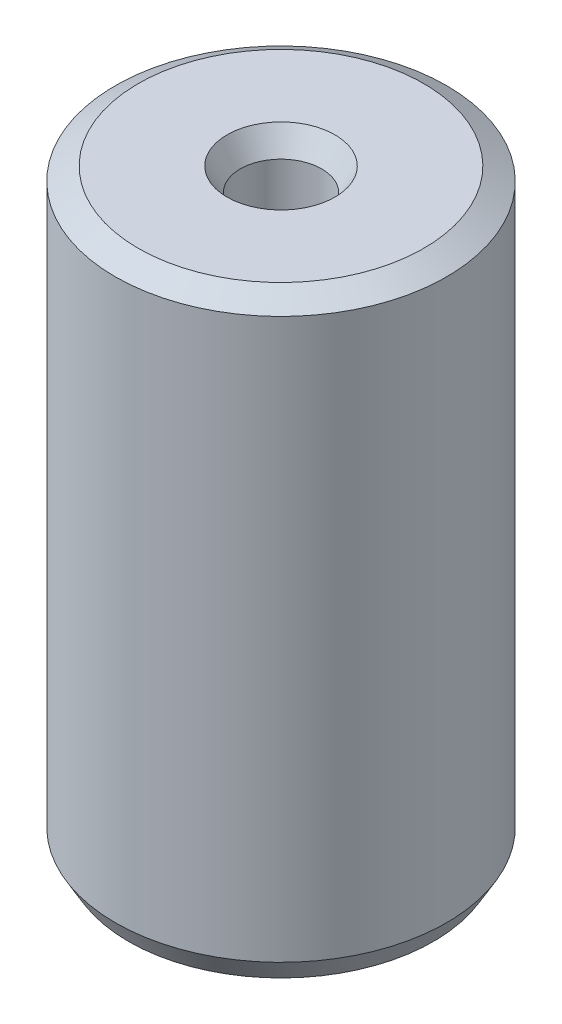
SolidWorks part; units mm, degrees
ref_plane "Front Plane" through (0, 0, 0) normal (0, 0, 1) x (1, 0, 0)
ref_plane "Top Plane" through (0, 0, 0) normal (0, 1, 0) x (1, 0, 0)
ref_plane "Right Plane" through (0, 0, 0) normal (1, 0, 0) x (0, 0, -1)
sketch "Sketch1" plane through (0, 0, 0) normal (0, 1, 0) x (1, 0, 0)
  circle A0 centre (0, 0) radius 5
  dimension "SLEEVE_OD" = 10
extrude "Boss-Extrude1" add sketch "Sketch1" along normal blind 17.9749
sketch "Sketch2" plane through (0, 0, 0) normal (0, 1, 0) x (1, 0, 0)
  circle A0 centre (0, 0) radius 1.23
  dimension "BORE_D" = 2.46
extrude "Cut-Extrude1" cut sketch "Sketch2" along normal through all
chamfer "Chamfer1" distance 0.3989 angle 60 4 edges at (0, 17.9749, 1.23) (0, 0, 1.23) (0, 0, 5) (0, 17.9749, 5) first distance on face at (0, 17.9749, 1.23) first distance on face at (0, 0, 1.23) first distance on face at (0, 17.9749, 5)
